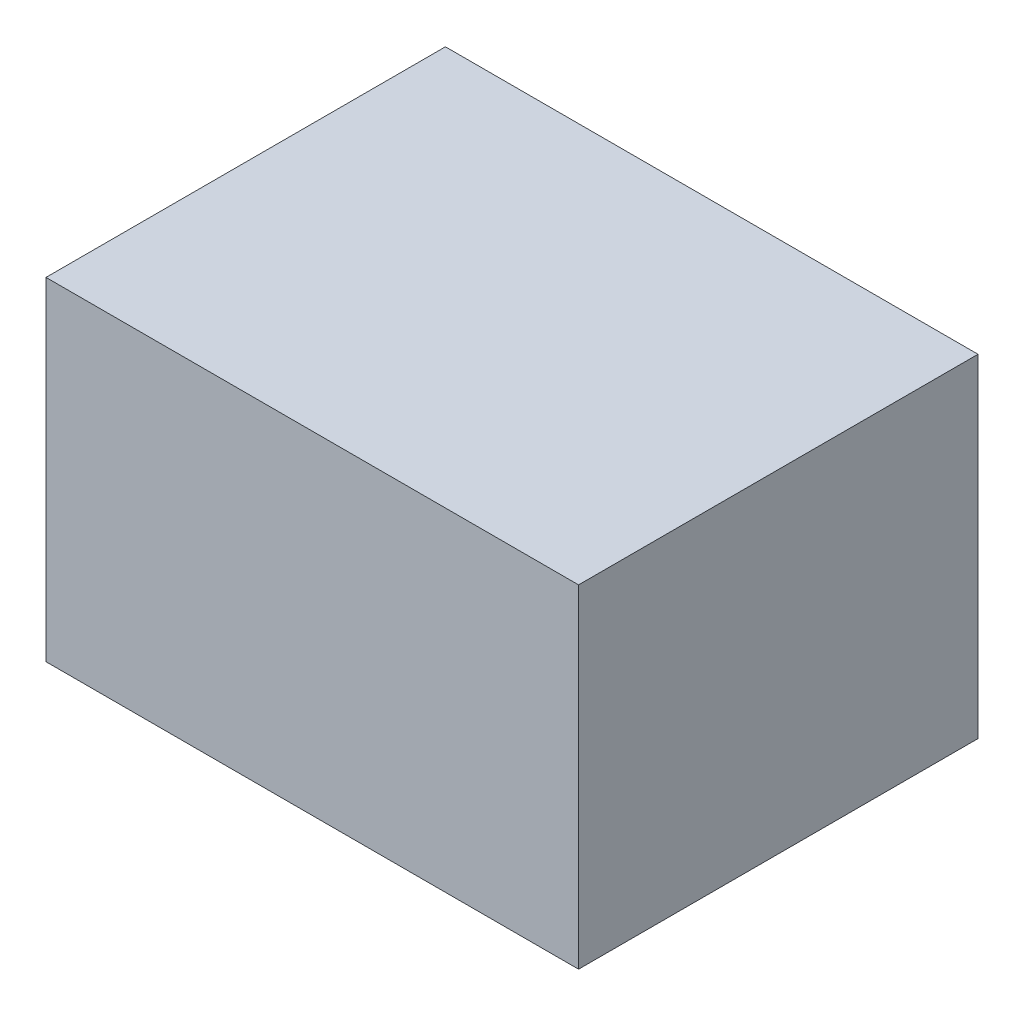
SolidWorks part; units mm, degrees
ref_plane "Front Plane" through (0, 0, 0) normal (0, 0, 1) x (1, 0, 0)
ref_plane "Top Plane" through (0, 0, 0) normal (0, 1, 0) x (1, 0, 0)
ref_plane "Right Plane" through (0, 0, 0) normal (1, 0, 0) x (0, 0, -1)
sketch "Sketch1" plane through (0, 0, 0) normal (1, 0, 0) x (0, 0, -1)
  line L1 (0, 0) -> (150, 0)
  line L2 (0, 0) -> (0, 125)
  line L3 (0, 125) -> (150, 125)
  line L4 (150, 0) -> (150, 125)
  dimension "D1" = 150
  dimension "D2" = 125
extrude "Boss-Extrude1" add sketch "Sketch1" along normal blind 200
